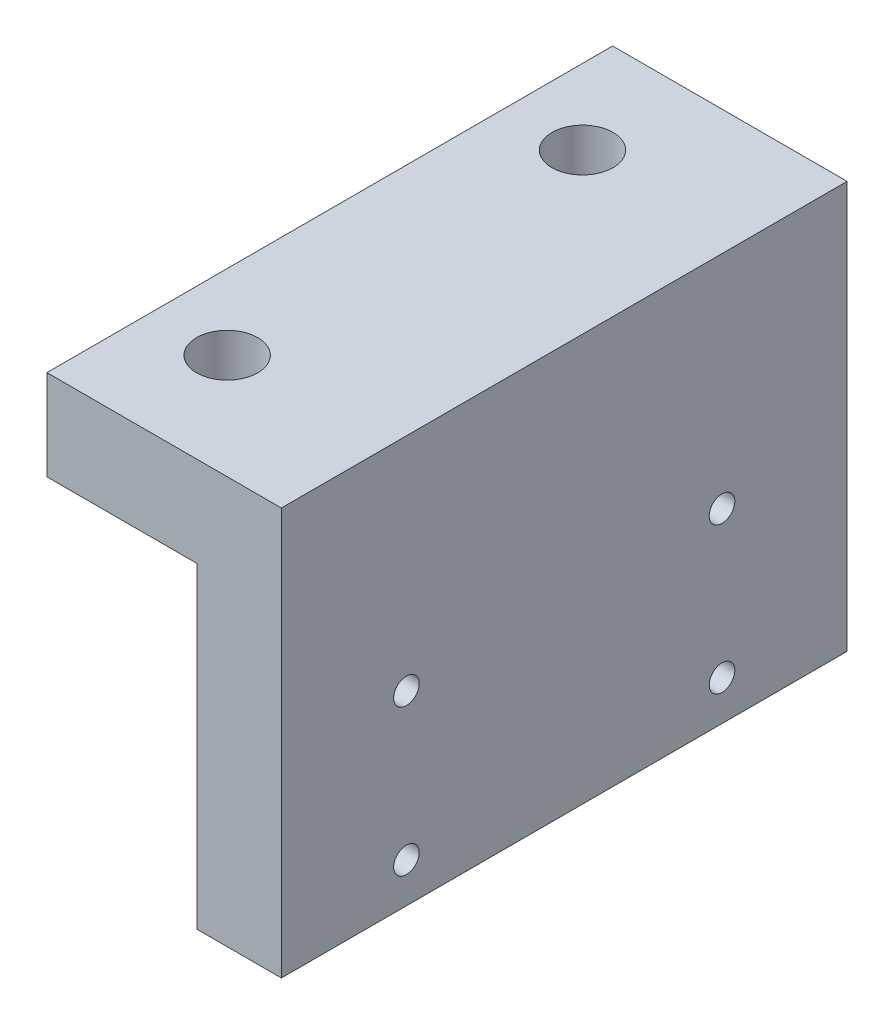
SolidWorks part; units mm, degrees
ref_plane "xy_plane" through (0, 0, 0) normal (0, 0, 1) x (1, 0, 0)
ref_plane "zx_plane" through (0, 0, 0) normal (0, 1, 0) x (1, 0, 0)
ref_plane "yz_plane" through (0, 0, 0) normal (1, 0, 0) x (0, 0, -1)
ref_axis "x_axis" through (-80.9, 0, 0) along (1, 0, 0)
ref_axis "y_axis" through (0, -50, 0) along (0, 1, 0)
ref_axis "z_axis" through (0, 0, -80.9) along (0, 0, 1)
ref_plane "zMin_plane" through (-5.15, -25.8375, 293.6) normal (0, 0, 1) x (-1, 0, 0)
ref_plane "zMax_plane" through (-5.15, -25.8375, 333.4) normal (0, 0, 1) x (-1, 0, 0)
ref_plane "zMid_plane" through (0, 0, 313.5) normal (0, 0, 1) x (1, 0, 0)
ref_point "zMid_plane_rootPoint"
ref_plane "proximalMountingSurface_plane" through (0, 0, 0) normal (0, 1, 0) x (1, 0, 0)
ref_point "proximalMountingSurface_plane_rootPoint"
ref_plane "distalMountingSurface_plane" through (0, 0, 0) normal (1, 0, 0) x (0, 0, -1)
ref_point "distalMountingSurface_plane_rootPoint"
sketch "projectionZ_sketch" plane through (0, 0, 0) normal (0, 0, 1) x (1, 0, 0)
  line L0 (3.175, -28.6375) -> (0, -28.6375)
  line L1 (0, -28.6375) -> (0, -3.175)
  line L2 (0, -3.175) -> (-10.56, -3.175)
  line L3 (-10.56, -3.175) -> (-10.56, 0)
  line L4 (-10.56, 0) -> (3.175, 0)
  line L5 (3.175, 0) -> (3.175, -28.6375)
  line L6 (55, 0) -> (-55, 0) construction
  line L7 (0, -50) -> (0, 50) construction
  line L8 (-10.3, -28.6375) -> (0, -28.6375) construction
  line L9 (0, -55) -> (0, 55) construction
  point P12 (0, 0)
  point P13 (0, 0)
  dimension "D1" = 3.175
  dimension "D2" = 13.735
extrude "mainBody_extrude" add sketch "projectionZ_sketch" along normal up to surface (333.4 mm away) from surface up to plane "zMax_plane" starting at plane "zMin_plane"
ref_plane "xMin_plane" through (-10.56, 0, 0) normal (1, 0, 0) x (0, 0, -1)
ref_plane "xMax_plane" through (3.175, 0, 0) normal (1, 0, 0) x (0, 0, -1)
sketch "nominalMountScrewPositionsHelper_sketch" plane through (0, 0, 0) normal (0, 1, 0) x (1, 0, 0)
  line L0 (-5.28, -301) -> (-5.28, -326)
  line L1 (0, 80.9) -> (0, -80.9) construction
  line L2 (-55, -313.5) -> (55, -313.5) construction
  line L5 (-10.56, -50) -> (-10.56, 50) construction
  point P4 (-5.28, -313.5)
  dimension "D1" = 25
  dimension "D2" = 5.28
sketch "nominalMountScrewPositions_sketch" plane through (0, 0, 0) normal (0, 1, 0) x (1, 0, 0)
  point P2 (-5.28, -326)
  point P4 (-5.28, -301)
sketch "proximalMountScrewHoles_sketch" plane through (0, 0, 0) normal (0, 1, 0) x (1, 0, 0)
  circle A0 centre (-5.28, -326) radius 2.15
  circle A1 centre (-5.28, -301) radius 2.15
  dimension "D1" = 4.3
sketch "switchMountHolePositions_sketch" plane through (0, 0, 0) normal (1, 0, 0) x (0, 0, -1)
  point P4 (-324.6, -15.5375)
  point P7 (-302.4, -15.5375)
  point P8 (-302.4, -25.8375)
  point P9 (-324.6, -25.8375)
sketch "bolsteredPlinthProjectionZ_sketch" plane through (0, 0, 297) normal (0, 0, 1) x (1, 0, 0)
  line L0 (-10.56, 0) -> (5.935, 0)
  line L1 (5.935, 0) -> (5.935, -28.6375)
  line L2 (3.175, -28.6375) -> (0, -6.35)
  line L3 (-10.56, -6.35) -> (-10.56, 0)
  line L4 (55, 0) -> (-55, 0) construction
  line L5 (-10.56, -50) -> (-10.56, 50) construction
  line L6 (0, -50) -> (0, 50) construction
  line L7 (0, -6.35) -> (-10.56, -6.35)
  line L9 (0, -28.6375) -> (0, -3.175) construction
  line L10 (3.175, 0) -> (3.175, -28.6375) construction
  line L12 (3.175, -28.6375) -> (5.935, -28.6375)
  line L13 (-80.9, 0) -> (80.9, 0) construction
  line L14 (3.175, -28.6375) -> (0, -28.6375) construction
  dimension "D1" = 6.35
  dimension "D2" = 2.76
extrude "bolsteredPlinth_extrude" add sketch "bolsteredPlinthProjectionZ_sketch" along normal up to surface (36.4 mm away) from surface up to plane "zMax_plane" starting at plane "zMin_plane"
sketch "proximalMountScrewHeadLands_sketch" plane through (0, 0, 0) normal (0, 1, 0) x (1, 0, 0)
  line L0 (-10.56, -331.28) -> (-5.28, -331.28)
  line L1 (-5.28, -320.72) -> (-10.56, -320.72)
  line L2 (-10.56, -320.72) -> (-10.56, -331.28)
  line L3 (-10.56, -306.28) -> (-5.28, -306.28)
  line L4 (-5.28, -295.72) -> (-10.56, -295.72)
  line L5 (-10.56, -295.72) -> (-10.56, -306.28)
  line L6 (-10.56, -50) -> (-10.56, 50) construction
  line L7 (-80.9, 0) -> (80.9, 0) construction
  circle A0 centre (-5.28, -326) radius 5.28 construction
  circle A1 centre (-5.28, -301) radius 5.28 construction
  arc A2 (-5.28, -331.28) -> (-5.28, -320.72) centre (-5.28, -326) ccw
  arc A3 (-5.28, -306.28) -> (-5.28, -295.72) centre (-5.28, -301) ccw
  dimension "D1" = 10.56
extrude "proximalMountHoleScrewHeadLands_cut" cut sketch "proximalMountScrewHeadLands_sketch" against normal up to next from vertex starting at point (-10.56, -3.175, 0)
extrude "proximalMountHoles_cut" cut sketch "proximalMountScrewHoles_sketch" against normal through all from surface starting at plane "proximalMountingSurface_plane"
hole_wizard "limitSwitchMountHoles_holeWizard" positions "Sketch6" profile "Sketch5" tap size "M3x0.5" standard "ANSI Metric" end condition through all
sketch "Sketch6" plane through (0, 0, 0) normal (1, 0, 0) x (0, 0, -1)
  point P12 (-302.4, -25.8375)
  point P14 (-302.4, -15.5375)
  point P16 (-324.6, -15.5375)
  point P18 (-324.6, -25.8375)
sketch "Sketch5" plane through (0, -25.8375, 302.4) normal (0, 1, 0) x (0, 0, 1)
  line L0 (0, 0) -> (0, 5.935)
  line L1 (0, 5.935) -> (0.9, 5.935)
  line L2 (0.9, 5.935) -> (0.9, 0)
  line L5 (0.9, 0) -> (0, 0)
  line L11 (0, -6.35) -> (0, 107.95) construction
  dimension "Thru Tap Drill Dia." = 1.8
  dimension "Thru Tap Drill Depth" = 5.935
cosmetic thread "Hole Thread1" parameters "D2"=3
cosmetic thread "Hole Thread2" parameters "D2"=3
cosmetic thread "Hole Thread3" parameters "D2"=3
cosmetic thread "Hole Thread4" parameters "D2"=3
equation "\"D1@projectionZ_sketch\"= \"externalParameters.this.thickness\""
equation "\"D1@zMin_plane\"= \"externalParameters.this.overhangZ\""
equation "\"D1@zMax_plane\" = \"externalParameters.this.overhangZ\""
equation "\"D1@nominalMountScrewPositionsHelper_sketch\"=25mm"
equation "\"D2@nominalMountScrewPositionsHelper_sketch\" =  ( \"externalParameters.this.extentX\" - \"externalParameters.this.thickness\" )  / 2"
equation "\"D2@projectionZ_sketch\"=\"externalParameters.this.extentX\""
equation "\"D1@proximalMountScrewHoles_sketch\"=\"externalParameters.this.proximalMountScrews.screw.clearanceHoleDiameter\""
equation "\"D1@proximalMountScrewHeadLands_sketch\" = \"externalParameters.this.proximalMountScrews.screw.headLandingDiameter\""
